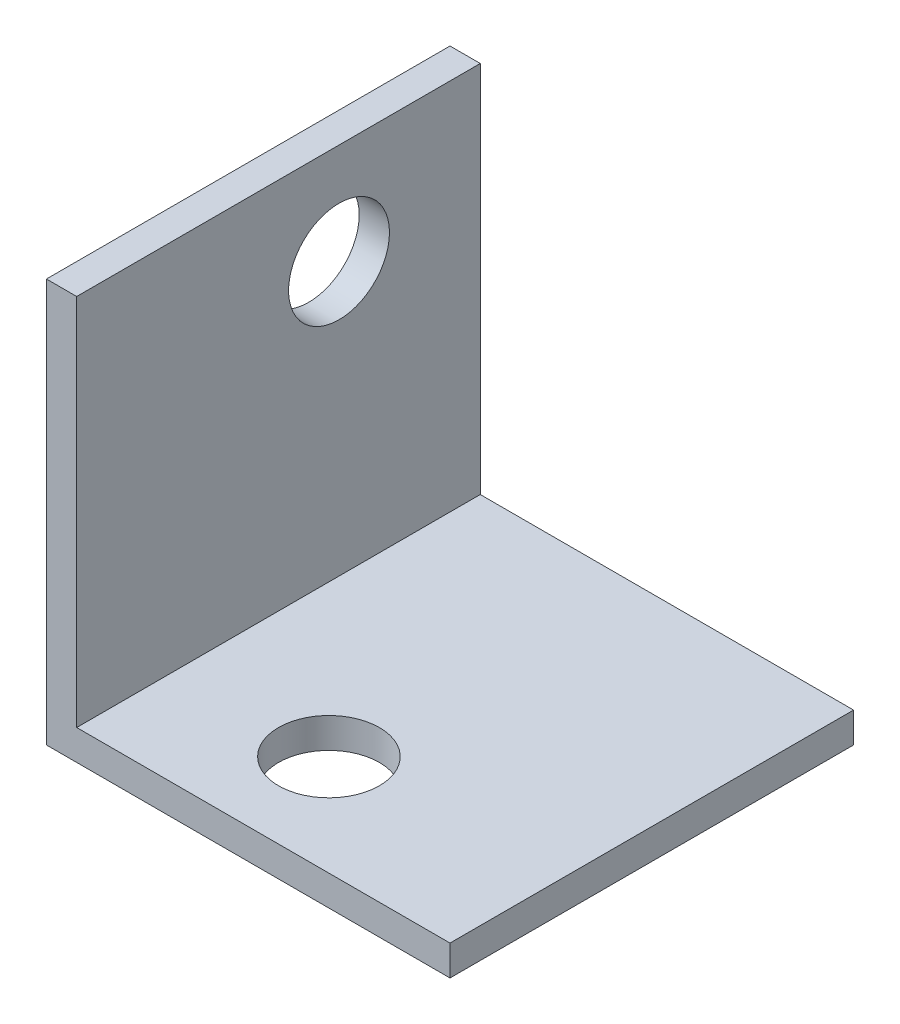
SolidWorks part; units mm, degrees
material "1060 Alloy"
ref_plane "xy" through (0, 0, 0) normal (0, 0, 1) x (1, 0, 0)
ref_plane "xz" through (0, 0, 0) normal (0, 1, 0) x (1, 0, 0)
ref_plane "yz" through (0, 0, 0) normal (1, 0, 0) x (0, 0, -1)
ref_axis "x" through (-1, 0, 0) along (1, 0, 0)
ref_axis "y" through (0, 21, 0) along (0, -1, 0)
ref_axis "z" through (0, 0, -2.575) along (0, 0, 1)
sketch "Sketch1" plane through (0, 0, 0) normal (0, 0, 1) x (1, 0, 0)
  line L0 (0, 0) -> (20, 0)
  line L1 (0, 0) -> (0, 20)
  dimension "D1" = 20
extrude "Extrude-Thin1" add sketch "Sketch1" along normal blind 20 thin thin type one direction wall 1.5
sketch "Sketch2" plane through (0, 0, 0) normal (0, -1, 0) x (-1, 0, 0)
  line L0 (-9, 0) -> (-9, -15) construction
  line L2 (-20, -20) -> (-20, 0) construction
  line L3 (-20, 0) -> (-1.5, 0) construction
  circle A0 centre (-9, -15) radius 2.5
  dimension "D2" = 5
  dimension "D1" = 15
  dimension "D3" = 11
extrude "Cut-Extrude1" cut sketch "Sketch2" against normal through all
sketch "Sketch3" plane through (1.5, 0, 0) normal (1, 0, 0) x (0, 0, -1)
  line L0 (-7, 15) -> (-7, 20) construction
  line L1 (-20, 20) -> (0, 20) construction
  line L2 (0, 1.5) -> (0, 20) construction
  circle A0 centre (-7, 15) radius 2.5
  dimension "D1" = 5
  dimension "D2" = 5
  dimension "D3" = 7
extrude "Cut-Extrude2" cut sketch "Sketch3" against normal through all
